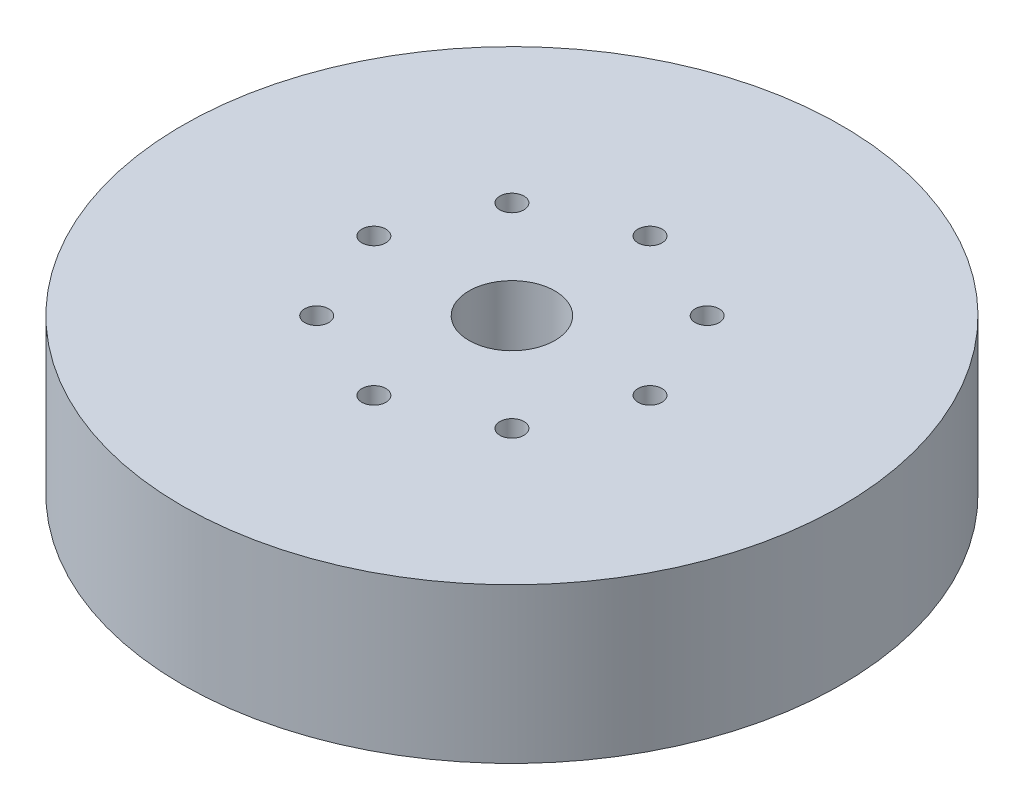
SolidWorks part; units mm, degrees
ref_plane "Front Plane" through (0, 0, 0) normal (0, 0, 1) x (1, 0, 0)
ref_plane "Top Plane" through (0, 0, 0) normal (0, 1, 0) x (1, 0, 0)
ref_plane "Right Plane" through (0, 0, 0) normal (1, 0, 0) x (0, 0, -1)
sketch "Sketch1" plane through (0, 0, 0) normal (0, 1, 0) x (1, 0, 0)
  circle A0 centre (0, 0) radius 57.5
  dimension "FLANGE_OD" = 115
extrude "Boss-Extrude1" add sketch "Sketch1" along normal blind 27
sketch "Sketch2" plane through (0, 0, 0) normal (0, 1, 0) x (1, 0, 0)
  circle A0 centre (0, 0) radius 7.5
  dimension "BORE_D" = 15
extrude "Cut-Extrude1" cut sketch "Sketch2" along normal through all
sketch "Sketch3" plane through (0, 27, 0) normal (0, 1, 0) x (1, 0, 0)
  circle A0 centre (0, 0) radius 24.0872 construction
  circle A1 centre (-24.0872, 0) radius 2.0951
  dimension "BOLT_D" = 4.1902
  dimension "BOLT_PCD" = 48.1744
extrude "Cut-Extrude2" cut sketch "Sketch3" against normal blind 21.4726
pattern_circular "CirPattern1" count 8 over 360 about axis through (0, 0, 0) along (0, 1, 0) of "Cut-Extrude2"
